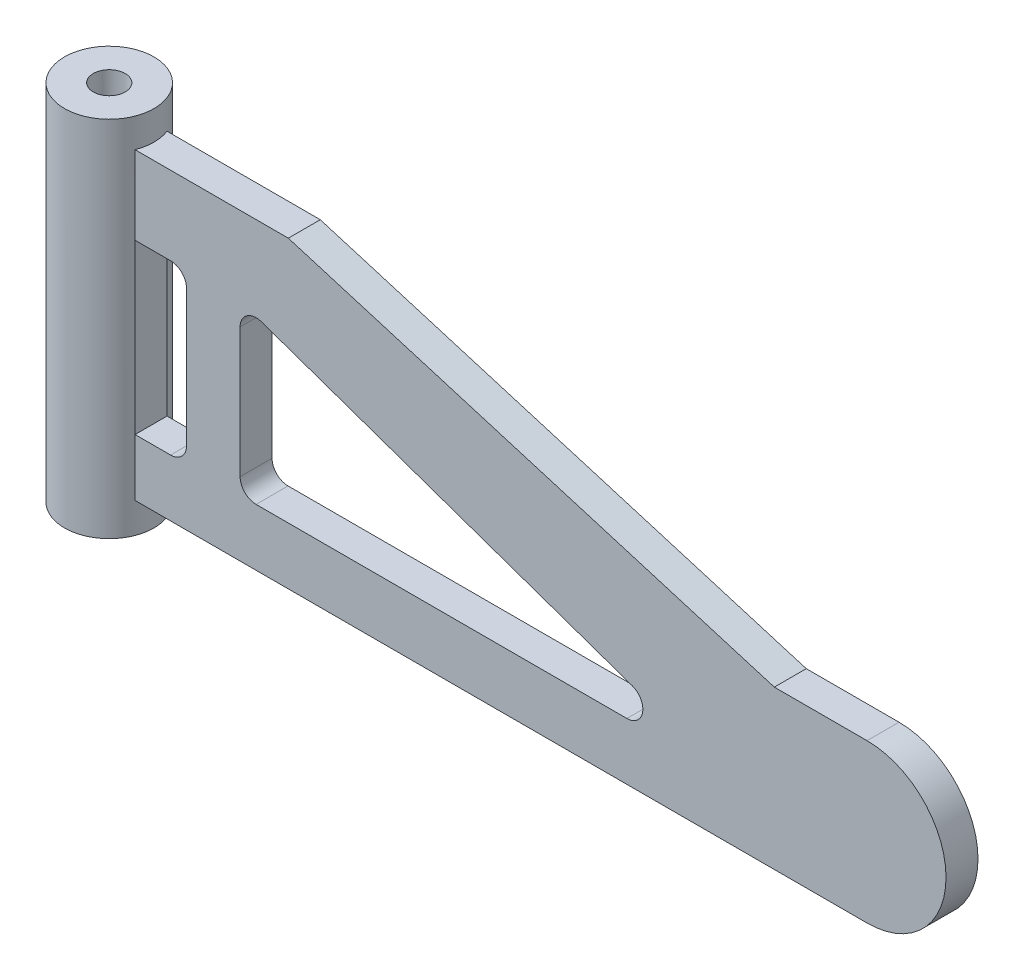
SolidWorks part; units mm, degrees
ref_plane "정면" through (0, 0, 0) normal (0, 0, 1) x (1, 0, 0)
ref_plane "윗면" through (0, 0, 0) normal (0, 1, 0) x (1, 0, 0)
ref_plane "우측면" through (0, 0, 0) normal (1, 0, 0) x (0, 0, -1)
sketch "스케치1" plane through (0, 0, 0) normal (0, 0, 1) x (1, 0, 0)
  line L0 (-104.6375, 39.8585) -> (-104.6375, -55.1415)
  line L1 (-104.6375, -55.1415) -> (151.3625, -55.1415)
  line L2 (-104.6375, 39.8585) -> (-29.6375, 39.8585)
  line L3 (-29.6375, 39.8585) -> (122.3625, -5.7415)
  line L4 (122.3625, -5.7415) -> (151.3625, -5.7415)
  arc A0 (151.3625, -5.7415) -> (151.3625, -55.1415) centre (151.3625, -30.4415) cw
  dimension "D1" = 75
  dimension "D2" = 95
  dimension "D3" = 256
  dimension "D4" = 45.6
  dimension "D5" = 152
extrude "보스-돌출1" add sketch "스케치1" along normal blind 10
sketch "스케치2" plane through (0, 39.8585, 0) normal (0, 1, 0) x (1, 0, 0)
  line L0 (-29.6375, 0) -> (-104.6375, 0) construction
  line L1 (-104.6375, -10) -> (-104.6375, 0) construction
  circle A0 centre (-90.6375, -5) radius 14
  dimension "D1" = 28
  dimension "D3" = 14
  dimension "D2" = 5
extrude "보스-돌출2" add sketch "스케치2" against normal blind 95
sketch "스케치3" plane through (0, 39.8585, 0) normal (0, 1, 0) x (1, 0, 0)
  circle A0 centre (-90.6375, -5) radius 14
extrude "보스-돌출3" add sketch "스케치3" along normal blind 9.1
sketch "스케치5" plane through (0, -55.1415, 0) normal (0, -1, 0) x (1, 0, 0)
  circle A0 centre (-90.6375, 5) radius 14
extrude "보스-돌출4" add sketch "스케치5" along normal blind 9.5
sketch "스케치6" plane through (0, 48.9585, 0) normal (0, 1, 0) x (1, 0, 0)
  circle A0 centre (-90.6375, -5) radius 5
  dimension "D1" = 10
extrude "컷-돌출1" cut sketch "스케치6" against normal through all both and the other way through all
sketch "스케치7" plane through (0, 0, 10) normal (0, 0, 1) x (1, 0, 0)
  line L0 (-77.5608, 39.8585) -> (-77.5608, -55.1415) construction
  line L1 (-77.5608, 15.3295) -> (-66.4563, 15.3295)
  line L2 (-77.5608, 15.3295) -> (-77.5608, -37.2911)
  line L3 (-77.5608, -37.2911) -> (-66.4563, -37.2911)
  line L4 (-61.4563, 10.3295) -> (-61.4563, -32.2911)
  line L5 (-44.7134, 8.2828) -> (-44.7134, -32.2911)
  line L6 (-39.7134, -37.2911) -> (76.245, -37.2911)
  line L7 (77.8964, -27.5717) -> (-38.0621, 13.0022)
  arc A0 (-66.4563, -37.2911) -> (-61.4563, -32.2911) centre (-66.4563, -32.2911) ccw
  arc A1 (-66.4563, 15.3295) -> (-61.4563, 10.3295) centre (-66.4563, 10.3295) cw
  arc A2 (77.8964, -27.5717) -> (76.245, -37.2911) centre (76.245, -32.2911) cw
  arc A3 (-39.7134, -37.2911) -> (-44.7134, -32.2911) centre (-39.7134, -32.2911) cw
  arc A4 (-44.7134, 8.2828) -> (-38.0621, 13.0022) centre (-39.7134, 8.2828) cw
  dimension "D1" = 5
extrude "컷-돌출2" cut sketch "스케치7" against normal blind 19.5
